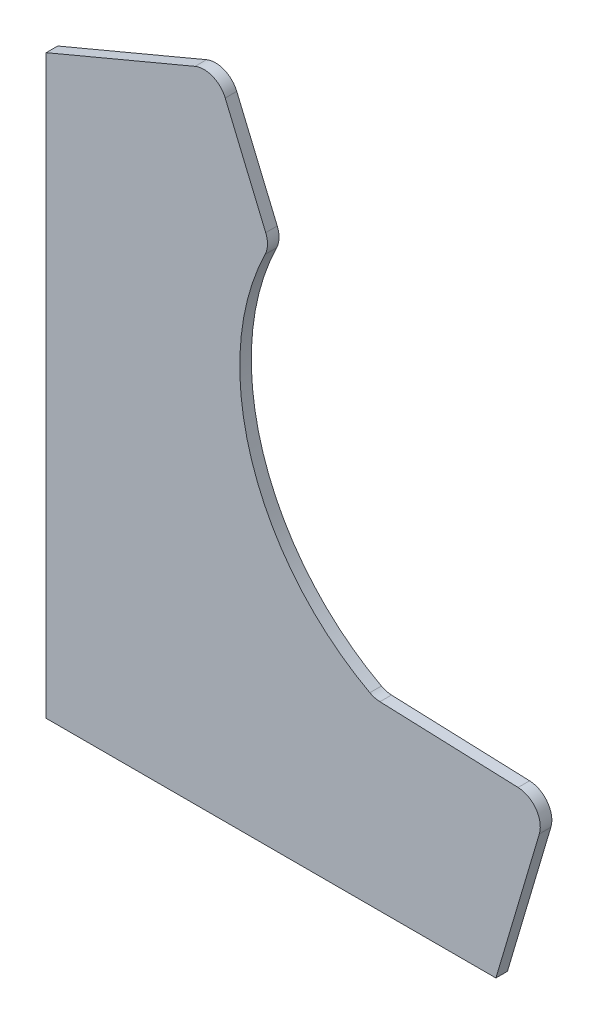
SolidWorks part; units mm, degrees
ref_plane "Plan de face" through (0, 0, 0) normal (0, 0, 1) x (1, 0, 0)
ref_plane "Plan de dessus" through (0, 0, 0) normal (0, 1, 0) x (1, 0, 0)
ref_plane "Plan de droite" through (0, 0, 0) normal (1, 0, 0) x (0, 0, -1)
sketch "Esquisse1" plane through (0, 0, 0) normal (0, 0, 1) x (1, 0, 0)
  line L0 (0, 0) -> (0, 500)
  line L1 (0, 0) -> (390, 0)
  line L2 (0, 500) -> (129.0626, 554.25)
  line L3 (155.25, 543.5626) -> (190.3729, 460.004)
  line L4 (390, 0) -> (427.6753, 127.0658)
  line L5 (409.2514, 152.737) -> (289.436, 157.2394)
  arc A0 (189.8854, 443.4335) -> (280.691, 159.6235) centre (382.69, 348.69) ccw
  arc A1 (155.25, 543.5626) -> (129.0626, 554.25) centre (136.8126, 535.8126) ccw
  arc A2 (409.2514, 152.737) -> (427.6753, 127.0658) centre (408.5004, 132.7512) cw
  arc A3 (189.8854, 443.4335) -> (190.3729, 460.004) centre (171.9355, 452.254) ccw
  arc A4 (289.436, 157.2394) -> (280.691, 159.6235) centre (290.187, 177.2253) cw
  point P12 (147.5, 562)
  point P15 (435, 151.7695)
  point P18 (193.9979, 451.38)
  dimension "D13" = 20
  dimension "D14" = 20
  dimension "D15" = 20
  dimension "D7" = 20
  dimension "D1" = 390
  dimension "D2" = 500
  dimension "D3" = 62
  dimension "D4" = 147.5
  dimension "D5" = 110.62
  dimension "D6" = 435
  dimension "D8" = 119.9
  dimension "D10" = 382.69
  dimension "D11" = 348.69
extrude "Boss.-Extru.1" add sketch "Esquisse1" along normal blind 10
